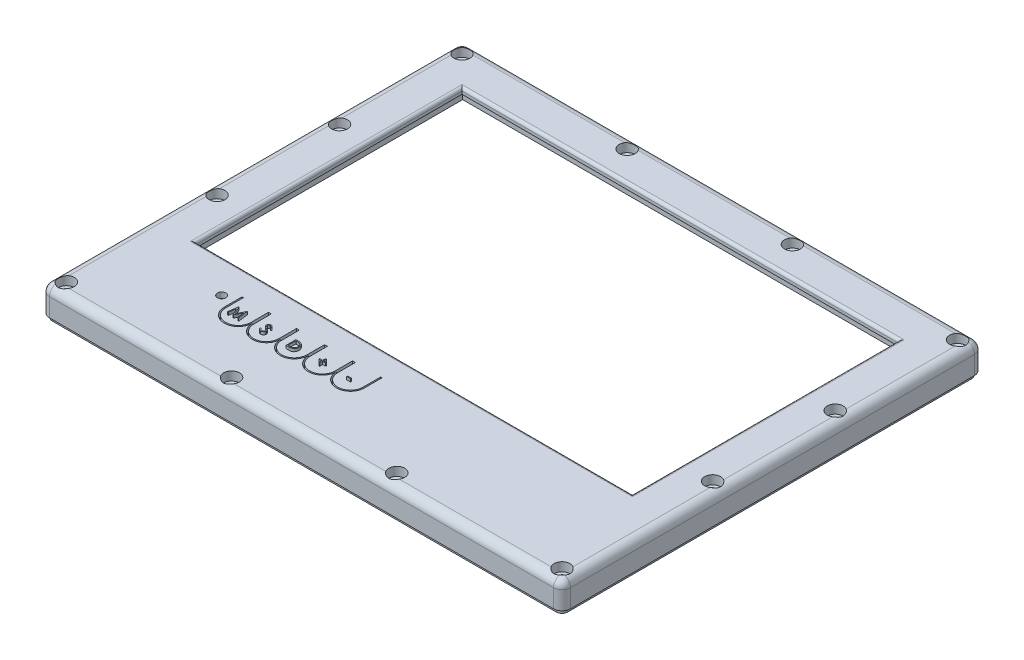
SolidWorks part; units mm, degrees
ref_plane "Front Plane" through (0, 0, 0) normal (0, 0, 1) x (1, 0, 0)
ref_plane "Top Plane" through (0, 0, 0) normal (0, 1, 0) x (1, 0, 0)
ref_plane "Right Plane" through (0, 0, 0) normal (1, 0, 0) x (0, 0, -1)
sketch "Sketch1" plane through (0, 0, 0) normal (0, 1, 0) x (1, 0, 0)
  line L1 (0, 0) -> (164.87, 0)
  line L2 (0, 0) -> (0, -104.3)
  line L3 (0, -104.3) -> (164.87, -104.3)
  line L4 (164.87, 0) -> (164.87, -104.3)
  line L5 (7.23, -7.46) -> (162.2, -7.46)
  line L6 (7.23, -7.46) -> (7.23, -101.93)
  line L7 (7.23, -101.93) -> (162.2, -101.93)
  line L8 (162.2, -7.46) -> (162.2, -101.93)
  line L9 (-4.77, 7.54) -> (174.2, 7.54)
  line L10 (-7.77, 4.54) -> (-7.77, -138.93)
  line L11 (-4.77, -141.93) -> (174.2, -141.93)
  line L12 (177.2, 4.54) -> (177.2, -138.93)
  arc A0 (174.2, -141.93) -> (177.2, -138.93) centre (174.2, -138.93) ccw
  arc A1 (-7.77, -138.93) -> (-4.77, -141.93) centre (-4.77, -138.93) ccw
  arc A2 (-4.77, 7.54) -> (-7.77, 4.54) centre (-4.77, 4.54) ccw
  arc A3 (174.2, 7.54) -> (177.2, 4.54) centre (174.2, 4.54) cw
  dimension "D11" = 3
  dimension "D1" = 104.3
  dimension "D2" = 164.87
  dimension "D3" = 2.67
  dimension "D4" = 2.37
  dimension "D5" = 7.46
  dimension "D6" = 7.23
  dimension "D7" = 15
  dimension "D8" = 15
  dimension "D9" = 15
  dimension "D10" = 40
extrude "Boss-Extrude1" add sketch "Sketch1" against normal blind 11 contours A3 L9 A2 L10 A1 L11 A0 L12 L1 L4 L3 L2 | L4 L1 L2 L3 L5 L8 L7 L6 region at (82.435, 0, 1.9509) region at (84.715, 0, -5.1619)
extrude "Cut-Extrude1" cut sketch "Sketch1<3>" along normal blind 9 from surface contours L4 L1 L2 L3 L5 L8 L7 L6 region at (82.435, 0, 1.9509) starting at face at (84.715, -11, 67.195)
sketch "Sketch1<3>" plane through (0, 0, 0) normal (0, 1, 0) x (1, 0, 0) same geometry as "Sketch1"
fillet "Fillet1" radius 3 8 edges at (-6.8913, 0, -6.6613) (-7.77, 0, 67.195) (-6.8913, 0, 141.0513) (84.715, 0, 141.93) (176.3213, 0, 141.0513) (177.2, 0, 67.195) (176.3213, 0, -6.6613) (84.715, 0, -7.54)
fillet "Fillet2" radius 1 4 edges at (84.715, 0, 101.93) (162.2, 0, 54.695) (7.23, 0, 54.695) (84.715, 0, 7.46)
sketch "Sketch2" plane through (0, -11, 0) normal (0, -1, 0) x (1, 0, 0)
  line L0 (-7.77, -4.54) -> (-7.77, 138.93) construction
  line L1 (-4.77, -7.54) -> (174.2, -7.54) construction
  line L2 (177.2, -4.54) -> (177.2, 138.93) construction
  line L3 (-4.77, 141.93) -> (174.2, 141.93) construction
  line L4 (164.87, 0) -> (164.87, 104.3) construction
  line L5 (164.87, 0) -> (168.54, 0)
  line L6 (164.87, 0) -> (164.87, 12.5)
  line L7 (164.87, 12.5) -> (168.54, 12.5)
  line L8 (168.54, 0) -> (168.54, 12.5)
  circle A0 centre (-3.27, -3.04) radius 1.6
  circle A1 centre (172.7, -3.04) radius 1.6
  circle A2 centre (172.7, 137.43) radius 1.6
  circle A3 centre (-3.27, 137.43) radius 1.6
  circle A4 centre (-3.27, 40.45) radius 1.6
  circle A5 centre (-3.27, 83.94) radius 1.6
  circle A6 centre (172.7, 40.45) radius 1.6
  circle A7 centre (172.7, 83.94) radius 1.6
  circle A8 centre (114.05, -3.04) radius 1.6
  circle A9 centre (55.38, -3.04) radius 1.6
  circle A10 centre (114.05, 137.43) radius 1.6
  circle A11 centre (55.38, 137.43) radius 1.6
  point P38 (0, 0)
  point P39 (0, 0)
  point P40 (0, 0)
  point P41 (0, 0)
  line M13 (164.87, 104.3) -> (164.87, 0)
  dimension "D1" = 3.2
  dimension "D4" = 3.2
  dimension "D6" = 3.2
  dimension "D8" = 3.2
  dimension "D9" = 3.2
  dimension "D10" = 3.2
  dimension "D13" = 3.2
  dimension "D14" = 3.2
  dimension "D17" = 3.2
  dimension "D18" = 3.2
  dimension "D19" = 3.2
  dimension "D20" = 3.2
  dimension "D2" = 4.5
  dimension "D3" = 4.5
  dimension "D5" = 4.5
  dimension "D7" = 4.5
  dimension "D11" = 43.49
  dimension "D12" = 43.49
  dimension "D15" = 12.5
  dimension "D16" = 3.67
  dimension "D21" = 58.65
  dimension "D22" = 58.65
extrude "Cut-Extrude2" cut sketch "Sketch2" against normal offset from surface (6.87 mm away) 2.13 contours L5 L8 L7 M13 region at (166.705, -11, 6.25) up to face at (82.435, -2, 52.15)
extrude "Cut-Extrude3" cut sketch "Sketch2<4>" against normal up to next contours A1 | A8 | A0 | A5 | A3 | A11 | A10 | A2 | A7 | A6 | A9 | A4 region at (-3.27, -11, -3.04) region at (172.7, -11, -3.04) region at (172.7, -11, 137.43) region at (-3.27, -11, 137.43) region at (-3.27, -11, 83.94) region at (172.7, -11, 40.45) region at (172.7, -11, 83.94) region at (114.05, -11, -3.04) region at (114.05, -11, 137.43) region at (55.38, -11, 137.43)
sketch "Sketch2<4>" plane through (0, -11, 0) normal (0, -1, 0) x (1, 0, 0) same geometry as "Sketch2"
sketch "Sketch3" plane through (0, -11, 0) normal (0, -1, 0) x (-1, 0, 0)
  line L0 (0, 0) -> (0, -104.3) construction
  line L1 (0, -110.85) -> (-83.11, -110.85)
  line L2 (0, -110.85) -> (0, -129.3)
  line L3 (0, -129.3) -> (-83.11, -129.3)
  line L4 (-83.11, -110.85) -> (-83.11, -129.3)
  line L5 (0, -110.85) -> (-22, -110.85)
  line L6 (0, -110.85) -> (0, -104.3)
  line L7 (0, -104.3) -> (-22, -104.3)
  line L8 (-22, -110.85) -> (-22, -104.3)
  line L9 (0, -104.3) -> (-164.87, -104.3) construction
  line M28 (0, -104.3) -> (-164.87, -104.3)
  dimension "D1" = 18.45
  dimension "D2" = 83.11
  dimension "D3" = 22
  dimension "D4" = 25
  dimension "D5" = 0
  dimension "D6" = 0
extrude "Cut-Extrude4" cut sketch "Sketch3" against normal offset from surface (9 mm away) 2 contours L8 L1 L6 M28 | L1 L4 L3 L2 region at (41.555, -11, 120.075) region at (11, -11, 107.575) up to face at (84.715, 0, 65.5283)
sketch "Sketch4" plane through (0, -2, 0) normal (0, -1, 0) x (1, 0, 0)
  line L0 (0, 0) -> (0, 129.3) construction
  line L1 (0, 129.3) -> (83.11, 129.3) construction
  circle A0 centre (28.4, 113.96) radius 1.5
  dimension "D1" = 3
  dimension "D2" = 28.4
  dimension "D3" = 15.34
extrude "Cut-Extrude5" cut sketch "Sketch4" against normal up to next
sketch "Sketch5" plane through (0, -2, 0) normal (0, -1, 0) x (1, 0, 0)
  line L0 (0, 129.3) -> (83.11, 129.3) construction
  line L1 (0, 0) -> (0, 129.3) construction
  line L2 (83.11, 110.85) -> (83.11, 129.3) construction
  circle A0 centre (4.99, 125.22) radius 3.225
  circle A1 centre (79.79, 125.22) radius 3.225
  circle A2 centre (79.79, 125.22) radius 1.725
  circle A3 centre (4.99, 125.22) radius 1.725
  point P6 (0, 0)
  dimension "D1" = 3.45
  dimension "D2" = 6.45
  dimension "D3" = 3.45
  dimension "D4" = 6.45
  dimension "D5" = 4.08
  dimension "D6" = 4.99
  dimension "D7" = 3.32
extrude "Boss-Extrude2" add sketch "Sketch5" along normal blind 7.5 contours A3 | A0 A3 | A2 | A1 A2 region at (1.8562, -2, 125.22) region at (76.6562, -2, 125.22) region at (79.79, -2, 125.22) region at (4.99, -2, 125.22)
extrude "Boss-Extrude3" add sketch "Sketch5<4>" along normal blind 1.5 from surface contours A2 | A3 region at (79.79, -2, 125.22) region at (4.99, -2, 125.22) starting at face at (79.79, -9.5, 121.995)
sketch "Sketch5<4>" plane through (0, -2, 0) normal (0, -1, 0) x (1, 0, 0) same geometry as "Sketch5"
sketch "Sketch6" plane through (0, -2, 0) normal (0, -1, 0) x (1, 0, 0)
  line L0 (83.11, 110.85) -> (83.11, 129.3) construction
  line L1 (22, 110.85) -> (83.11, 110.85) construction
  line L4 (81.715, 110.85) -> (81.715, 117.095)
  line L5 (77.245, 121.565) -> (77.235, 121.565)
  line L6 (72.765, 110.85) -> (72.765, 117.095)
  line L8 (71.765, 110.85) -> (71.765, 117.095)
  line L9 (67.295, 121.565) -> (67.285, 121.565)
  line L10 (62.815, 110.85) -> (62.815, 117.095)
  line L12 (61.815, 110.85) -> (61.815, 117.095)
  line L13 (57.345, 121.565) -> (57.335, 121.565)
  line L14 (52.865, 110.85) -> (52.865, 117.095)
  line L16 (51.865, 110.85) -> (51.865, 117.095)
  line L17 (47.395, 121.565) -> (47.385, 121.565)
  line L18 (42.915, 110.85) -> (42.915, 117.095)
  line L20 (41.915, 110.85) -> (41.915, 117.095)
  line L21 (37.445, 121.565) -> (37.435, 121.565)
  line L22 (32.965, 110.85) -> (32.965, 117.095)
  line L23 (82.215, 110.85) -> (82.215, 117.095)
  line L24 (77.245, 122.065) -> (77.235, 122.065)
  line L25 (72.265, 110.85) -> (72.265, 117.095)
  line L26 (72.265, 110.85) -> (72.265, 117.095)
  line L27 (67.295, 122.065) -> (67.285, 122.065)
  line L28 (62.315, 110.85) -> (62.315, 117.095)
  line L29 (62.315, 110.85) -> (62.315, 117.095)
  line L30 (57.345, 122.065) -> (57.335, 122.065)
  line L31 (52.365, 110.85) -> (52.365, 117.095)
  line L32 (52.365, 110.85) -> (52.365, 117.095)
  line L33 (47.395, 122.065) -> (47.385, 122.065)
  line L34 (42.415, 110.85) -> (42.415, 117.095)
  line L35 (32.465, 110.85) -> (32.465, 117.095)
  line L36 (37.445, 122.065) -> (37.435, 122.065)
  line L37 (42.415, 110.85) -> (42.415, 117.095)
  line L38 (32.965, 110.85) -> (32.465, 110.85)
  line L39 (42.415, 110.85) -> (41.915, 110.85)
  line L40 (51.865, 110.85) -> (52.365, 110.85)
  line L41 (52.865, 110.85) -> (52.365, 110.85)
  line L42 (42.915, 110.85) -> (42.415, 110.85)
  line L43 (61.815, 110.85) -> (62.315, 110.85)
  line L44 (62.815, 110.85) -> (62.315, 110.85)
  circle A0 centre (77.24, 117.09) radius 2.15
  circle A1 centre (67.29, 117.09) radius 2.15
  circle A2 centre (57.34, 117.09) radius 2.15
  circle A3 centre (47.39, 117.09) radius 2.15
  circle A4 centre (37.44, 117.09) radius 2.15
  arc A5 (37.435, 121.565) -> (32.965, 117.095) centre (37.435, 117.095) ccw
  arc A6 (41.915, 117.095) -> (37.445, 121.565) centre (37.445, 117.095) ccw
  arc A7 (47.385, 121.565) -> (42.915, 117.095) centre (47.385, 117.095) ccw
  arc A8 (51.865, 117.095) -> (47.395, 121.565) centre (47.395, 117.095) ccw
  arc A9 (57.335, 121.565) -> (52.865, 117.095) centre (57.335, 117.095) ccw
  arc A10 (61.815, 117.095) -> (57.345, 121.565) centre (57.345, 117.095) ccw
  arc A11 (67.285, 121.565) -> (62.815, 117.095) centre (67.285, 117.095) ccw
  arc A12 (71.765, 117.095) -> (67.295, 121.565) centre (67.295, 117.095) ccw
  arc A13 (77.235, 121.565) -> (72.765, 117.095) centre (77.235, 117.095) ccw
  arc A14 (81.715, 117.095) -> (77.245, 121.565) centre (77.245, 117.095) ccw
  arc A15 (82.215, 117.095) -> (77.245, 122.065) centre (77.245, 117.095) ccw
  arc A16 (77.235, 122.065) -> (72.265, 117.095) centre (77.235, 117.095) ccw
  arc A17 (72.265, 117.095) -> (67.295, 122.065) centre (67.295, 117.095) ccw
  arc A18 (67.285, 122.065) -> (62.315, 117.095) centre (67.285, 117.095) ccw
  arc A19 (62.315, 117.095) -> (57.345, 122.065) centre (57.345, 117.095) ccw
  arc A20 (57.335, 122.065) -> (52.365, 117.095) centre (57.335, 117.095) ccw
  arc A21 (52.365, 117.095) -> (47.395, 122.065) centre (47.395, 117.095) ccw
  arc A22 (47.385, 122.065) -> (42.415, 117.095) centre (47.385, 117.095) ccw
  arc A23 (37.435, 122.065) -> (32.465, 117.095) centre (37.435, 117.095) ccw
  arc A24 (42.415, 117.095) -> (37.445, 122.065) centre (37.445, 117.095) ccw
  line M9 (22, 110.85) -> (83.11, 110.85)
  dimension "D1" = 4.3
  dimension "D2" = 4.3
  dimension "D3" = 4.3
  dimension "D4" = 4.3
  dimension "D5" = 4.3
  dimension "D23" = 4.47
  dimension "D6" = 9.95
  dimension "D7" = 9.95
  dimension "D8" = 9.95
  dimension "D9" = 9.95
  dimension "D10" = 5.87
  dimension "D11" = 6.24
  dimension "D12" = 4.475
  dimension "D13" = 4.475
  dimension "D14" = 4.475
  dimension "D15" = 4.475
  dimension "D16" = 4.475
  dimension "D17" = 4.475
  dimension "D18" = 4.475
  dimension "D19" = 4.475
  dimension "D20" = 4.475
  dimension "D21" = 4.475
  dimension "D22" = 4.475
  dimension "D24" = 0.5
  dimension "D25" = 0.5
extrude "Cut-Extrude6" cut sketch "Sketch6" against normal blind 2.86 contours L24 A16 L25 L6 A13 L5 A14 L4 L23 A15 M9 | L27 A18 L28 L10 A11 L9 A12 L8 L25 A17 M9 | L30 A20 L31 L14 A9 L13 A10 L12 L28 A19 M9 | L33 A22 L34 L18 A7 L17 A8 L16 L31 A21 M9 | L34 A24 L36 A23 L35 L22 A5 L21 A6 L20 M9 region at (81.8649, -2, 113.9725) region at (72.015, -2, 110.9999) region at (62.065, -2, 110.9999) region at (52.115, -2, 110.9999) region at (42.165, -2, 110.9999)
extrude "Boss-Extrude5" add sketch "Sketch6<3>" along normal blind 2.86 contours A0 | A1 | A2 | A3 | A4 region at (77.24, -2, 117.09) region at (67.29, -2, 117.09) region at (57.34, -2, 117.09) region at (47.39, -2, 117.09) region at (37.44, -2, 117.09)
sketch "Sketch6<3>" plane through (0, -2, 0) normal (0, -1, 0) x (1, 0, 0) same geometry as "Sketch6"
sketch "Sketch7" plane through (0, 0, 0) normal (0, 1, 0) x (1, 0, 0)
  text T0 "M"
  text T1 "S"
  text T2 "D"
  text T3 "+"
  text T4 "-"
  point P5 (0, 0)
  point P6 (66.0034, -118.8722)
  point P7 (76.5813, -118.8921)
  point P8 (55.494, -117.263)
  point P9 (0, 0)
  point P10 (0, 0)
  point P11 (0, 0)
  point P12 (0, 0)
extrude "Boss-Extrude6" add sketch "Sketch7" along normal blind 1
sketch "Sketch8" plane through (0, -11, 0) normal (0, -1, 0) x (1, 0, 0)
  line L0 (164.87, 12.5) -> (164.87, 104.3) construction
  line L1 (86.11, 110.85) -> (164.87, 110.85)
  line L2 (86.11, 110.85) -> (86.11, 129.3)
  line L3 (86.11, 129.3) -> (164.87, 129.3)
  line L4 (164.87, 110.85) -> (164.87, 129.3)
  line L5 (22, 110.85) -> (83.11, 110.85) construction
  line L6 (0, 129.3) -> (83.11, 129.3) construction
  line L7 (83.11, 110.85) -> (83.11, 129.3) construction
  dimension "D1" = 3
extrude "Cut-Extrude7" cut sketch "Sketch8" against normal offset from surface (8 mm away) 3 up to face at (57.3181, 0, 117.3483)
sketch "Sketch9" plane through (0, 0, 0) normal (0, 1, 0) x (1, 0, 0)
  circle A0 centre (-3.27, 3.04) radius 2.825
  circle A1 centre (55.38, 3.04) radius 2.825
  circle A2 centre (114.05, 3.04) radius 2.825
  circle A3 centre (172.7, 3.04) radius 2.825
  circle A4 centre (172.7, -40.45) radius 2.825
  circle A5 centre (172.7, -83.94) radius 2.825
  circle A6 centre (172.7, -137.43) radius 2.825
  circle A7 centre (114.05, -137.43) radius 2.825
  circle A8 centre (55.38, -137.43) radius 2.825
  circle A9 centre (-3.27, -137.43) radius 2.825
  circle A10 centre (-3.27, -83.94) radius 2.825
  circle A11 centre (-3.27, -40.45) radius 2.825
  dimension "D1" = 5.65
  dimension "D2" = 5.65
  dimension "D3" = 5.65
  dimension "D4" = 5.65
  dimension "D5" = 5.65
  dimension "D6" = 5.65
  dimension "D7" = 5.65
  dimension "D8" = 5.65
  dimension "D9" = 5.65
  dimension "D10" = 5.65
  dimension "D11" = 5.65
  dimension "D12" = 5.65
extrude "Cut-Extrude8" cut sketch "Sketch9" against normal blind 3.13
sketch "Sketch12" plane through (0, -11, 0) normal (0, -1, 0) x (1, 0, 0)
  line L0 (-4.77, -7.54) -> (174.2, -7.54)
  line L1 (177.2, -4.54) -> (177.2, 138.93)
  line L2 (-4.77, 141.93) -> (174.2, 141.93)
  line L3 (-7.77, -4.54) -> (-7.77, 138.93)
  line L8 (176.2, -4.54) -> (176.2, 138.93)
  line L9 (-4.77, -6.54) -> (174.2, -6.54)
  line L10 (176.2, -4.54) -> (176.2, 138.93)
  line L11 (-4.77, -6.54) -> (174.2, -6.54)
  line L18 (-6.77, -4.54) -> (-6.77, 138.93)
  line L19 (-4.77, 140.93) -> (174.2, 140.93)
  line L20 (-6.77, -4.54) -> (-6.77, 138.93)
  line L21 (-4.77, 140.93) -> (174.2, 140.93)
  arc A0 (174.2, -7.54) -> (177.2, -4.54) centre (174.2, -4.54) ccw
  arc A1 (177.2, 138.93) -> (174.2, 141.93) centre (174.2, 138.93) ccw
  arc A2 (-4.77, 141.93) -> (-7.77, 138.93) centre (-4.77, 138.93) ccw
  arc A3 (-7.77, -4.54) -> (-4.77, -7.54) centre (-4.77, -4.54) ccw
  arc A6 (176.2, 138.93) -> (174.2, 140.93) centre (174.2, 138.93) ccw
  arc A7 (174.2, -6.54) -> (176.2, -4.54) centre (174.2, -4.54) ccw
  arc A8 (176.2, 138.93) -> (174.2, 140.93) centre (174.2, 138.93) ccw
  arc A9 (174.2, -6.54) -> (176.2, -4.54) centre (174.2, -4.54) ccw
  arc A14 (-6.77, -4.54) -> (-4.77, -6.54) centre (-4.77, -4.54) ccw
  arc A15 (-4.77, 140.93) -> (-6.77, 138.93) centre (-4.77, 138.93) ccw
  arc A16 (-6.77, -4.54) -> (-4.77, -6.54) centre (-4.77, -4.54) ccw
  arc A17 (-4.77, 140.93) -> (-6.77, 138.93) centre (-4.77, 138.93) ccw
  dimension "D1" = 1
  dimension "D2" = 1
  dimension "D3" = 1
extrude "Cut-Extrude9" cut sketch "Sketch12" against normal blind 1.5
